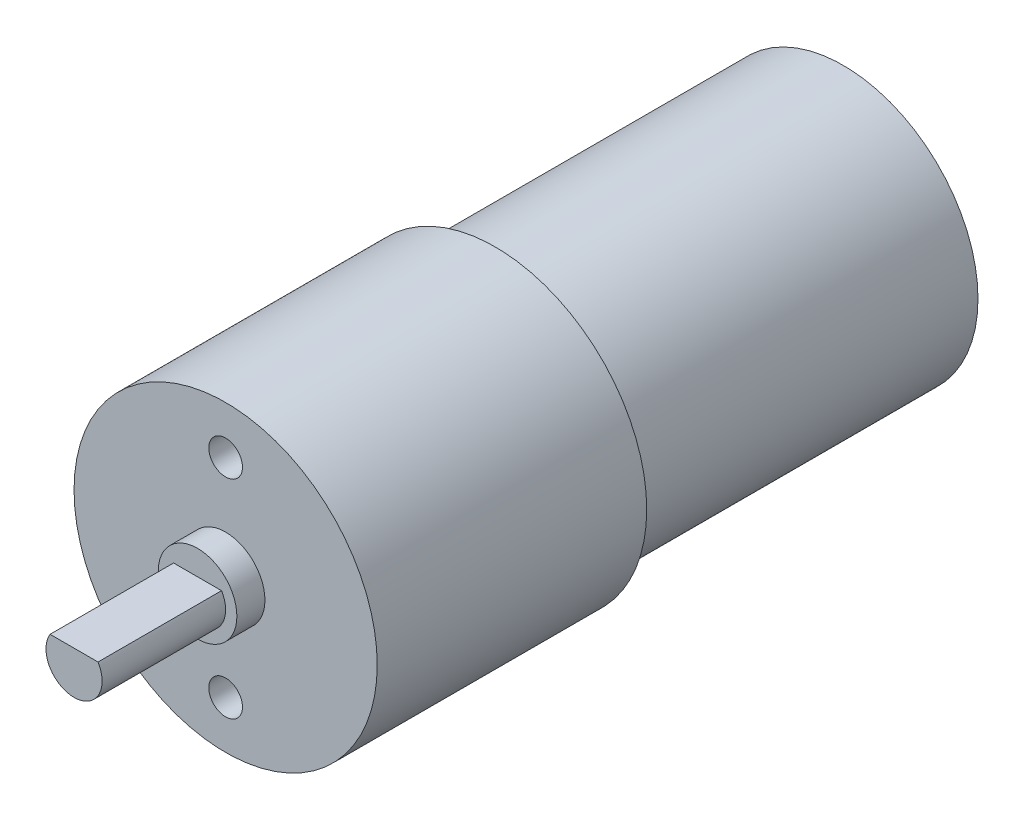
SolidWorks part; units mm, degrees
ref_plane "Front Plane" through (0, 0, 0) normal (0, 0, 1) x (1, 0, 0)
ref_plane "Top Plane" through (0, 0, 0) normal (0, 1, 0) x (1, 0, 0)
ref_plane "Right Plane" through (0, 0, 0) normal (1, 0, 0) x (0, 0, -1)
sketch "Sketch1" plane through (0, 0, 0) normal (0, 0, 1) x (1, 0, 0)
  circle A0 centre (0, 0) radius 13.5
  circle A1 centre (0, 0) radius 12
  point P5 (0.4763, 0)
  dimension "D1" = 27
  dimension "D2" = 24
extrude "Boss-Extrude1" add sketch "Sketch1" against normal blind 24 contours A0
extrude "Boss-Extrude2" add sketch "Sketch1<3>" against normal blind 31 from surface contours A1 region at (0, 0, 0) starting at face at (13.5, 0, -24)
sketch "Sketch1<3>" plane through (0, 0, 0) normal (0, 0, 1) x (1, 0, 0) same geometry as "Sketch1"
sketch "Sketch2" plane through (0, 0, 0) normal (0, 0, 1) x (1, 0, 0)
  line L0 (-2.1354, 1.3) -> (2.1354, 1.3)
  line L1 (-2.4495, -2.5) -> (2.4495, -2.5) construction
  circle A0 centre (0, 0) radius 3.5
  circle A1 centre (0, 0) radius 2.5
  dimension "D1" = 7
  dimension "D2" = 5
  dimension "D3" = 3.8
extrude "Boss-Extrude3" add sketch "Sketch2" along normal blind 2.5 contours A0
extrude "Boss-Extrude4" add sketch "Sketch2<3>" along normal blind 11 from surface contours L0 A1 region at (0, -0.4054, 0) starting at face at (3.5, 0, 2.5)
sketch "Sketch2<3>" plane through (0, 0, 0) normal (0, 0, 1) x (1, 0, 0) same geometry as "Sketch2"
sketch "Sketch3" plane through (0, 0, 0) normal (0, 0, 1) x (1, 0, 0)
  circle A0 centre (0, 0) radius 7.75 construction
  circle A1 centre (0, 9.25) radius 1.5
  circle A2 centre (0, -9.25) radius 1.5
  point P7 (0, -9.6542)
  point P8 (0, 9.7132)
  dimension "D1" = 15.5
  dimension "D2" = 3
extrude "Cut-Extrude1" cut sketch "Sketch3" against normal blind 4
